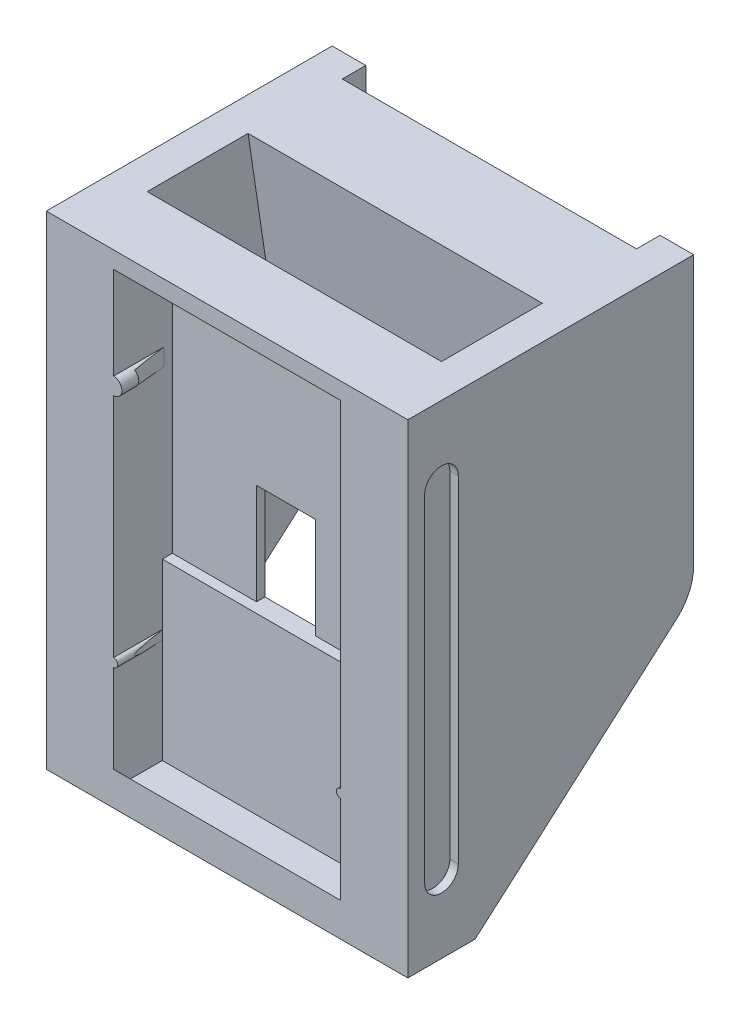
SolidWorks part; units mm, degrees
ref_plane "Front Plane" through (0, 0, 0) normal (0, 0, 1) x (1, 0, 0)
ref_plane "Top Plane" through (0, 0, 0) normal (0, 1, 0) x (1, 0, 0)
ref_plane "Right Plane" through (0, 0, 0) normal (1, 0, 0) x (0, 0, -1)
sketch "Sketch2" plane through (0, 0, 0) normal (0, 0, 1) x (1, 0, 0)
  line L1 (-6.75, -13.375) -> (6.75, -13.375) construction
  line L2 (-6.75, -13.375) -> (-6.75, 13.375)
  line L3 (-6.75, 13.375) -> (6.75, 13.375)
  line L4 (6.75, -13.375) -> (6.75, 13.375)
  line L5 (-6.75, -13.375) -> (6.75, 13.375) construction
  line L6 (-6.75, 13.375) -> (6.75, -13.375) construction
  line L13 (-1.75, 3) -> (1.75, 3)
  line L14 (-1.75, 3) -> (-1.75, -3)
  line L15 (-1.75, -3) -> (1.75, -3)
  line L16 (1.75, 3) -> (1.75, -3)
  line L17 (-1.75, 3) -> (1.75, -3) construction
  line L18 (-1.75, -3) -> (1.75, 3) construction
  line L24 (-6.75, -3) -> (6.75, -3)
  line L25 (-6.75, -3) -> (-6.75, -13.375)
  line L26 (-6.75, -13.375) -> (6.75, -13.375)
  line L27 (6.75, -3) -> (6.75, -13.375)
  point P0 (0, 0)
  point P23 (0, 0)
  dimension "D1" = 13.5
  dimension "D2" = 26.75
  dimension "D5" = 3.5
  dimension "D6" = 6
extrude "Boss-Extrude2" add sketch "Sketch2" against normal blind 0.5 contours L2 L24 L14 L13 L16 L4 L3 | L2 L26 L4 L24 L15 region at (0, -8.1875, 0) region at (0, 5.732, 0)
extrude "Boss-Extrude3" add sketch "Sketch2<5>" along normal blind 0.6 contours L2 L26 L4 L24 L15 region at (0, -8.1875, 0)
sketch "Sketch2<5>" plane through (0, 0, 0) normal (0, 0, 1) x (1, 0, 0) same geometry as "Sketch2"
sketch "Sketch4" plane through (0, 0, -0.5) normal (0, 0, -1) x (-1, 0, 0)
  line L1 (-10.75, 14.375) -> (10.75, 14.375)
  line L2 (-10.75, 14.375) -> (-10.75, -14.375)
  line L3 (-10.75, -14.375) -> (10.75, -14.375)
  line L4 (6.75, -13.375) -> (6.75, 13.375)
  line L5 (6.75, 13.375) -> (-6.75, 13.375)
  line L6 (-6.75, 13.375) -> (-6.75, -13.375)
  line L7 (-6.75, -13.375) -> (6.75, -13.375)
  line L8 (6.75, -13.375) -> (6.75, 13.375)
  line L9 (6.75, 13.375) -> (-6.75, 13.375)
  line L10 (-6.75, 13.375) -> (-6.75, -13.375)
  line L11 (-6.75, -13.375) -> (6.75, -13.375)
  line L12 (10.75, 14.375) -> (10.75, -14.375)
  line L13 (-10.75, 14.375) -> (10.75, -14.375) construction
  line L14 (-10.75, -14.375) -> (10.75, 14.375) construction
  point P2 (0, 0)
  line M13 (6.75, -13.375) -> (6.75, 13.375)
  line M14 (6.75, 13.375) -> (-6.75, 13.375)
  line M15 (-6.75, 13.375) -> (-6.75, -13.375)
  line M16 (-6.75, -13.375) -> (6.75, -13.375)
  dimension "D2" = 4
  dimension "D3" = 1
  dimension "D1" = 0
extrude "Boss-Extrude4" add sketch "Sketch4" against normal blind 3 contours L12 L1 L2 L3 M13 M16 M15 M14 region at (0, 14.016, -0.5)
sketch "Sketch5" plane through (0, 0, 2.5) normal (0, 0, 1) x (1, 0, 0)
  line L1 (-6.75, -13.375) -> (-6.75, -3) construction
  line L2 (6.75, 13.375) -> (6.75, -13.375) construction
  line L3 (-6.75, -13.375) -> (-6.75, 13.375) construction
  line L4 (-10.75, 14.375) -> (-10.75, -14.375)
  line L5 (-10.75, -14.375) -> (10.75, -14.375)
  line L6 (10.75, -14.375) -> (10.75, 14.375)
  line L7 (10.75, 14.375) -> (-10.75, 14.375)
  line L8 (-10.75, 14.375) -> (-10.75, -14.375)
  line L9 (-10.75, -14.375) -> (10.75, -14.375)
  line L10 (10.75, -14.375) -> (10.75, 14.375)
  line L11 (10.75, 14.375) -> (-10.75, 14.375)
  line L12 (-6.75, -13.375) -> (6.75, -13.375) construction
  line L13 (-6.75, 13.375) -> (6.75, 13.375) construction
  line L14 (-6.75, -7.125) -> (-6.75, -11.375)
  line L15 (-6.75, -11.375) -> (6.75, -11.375)
  line L16 (6.75, -11.375) -> (6.75, -7.125)
  line L17 (6.75, -6.625) -> (6.75, 13.375)
  line L18 (6.75, 13.375) -> (-6.75, 13.375)
  line L19 (-6.75, 13.375) -> (-6.75, 7.875)
  line L20 (-6.75, 6.875) -> (-6.75, -6.625)
  line L21 (6.75, -13.375) -> (-6.75, -13.375) construction
  arc A0 (-6.75, -7.125) -> (-6.75, -6.625) centre (-6.75, -6.875) ccw
  arc A1 (6.75, -6.625) -> (6.75, -7.125) centre (6.75, -6.875) ccw
  arc A2 (-6.75, 6.875) -> (-6.75, 7.875) centre (-6.75, 7.375) ccw
  dimension "D3" = 0.5
  dimension "D4" = 1
  dimension "D2" = 6.5
  dimension "D5" = 6
  dimension "D6" = 2
  dimension "D1" = 0
extrude "Boss-Extrude5" add sketch "Sketch5" along normal blind 1
chamfer "Chamfer1" distance 2 distance2 0.25 3 edges at (6.75, -6.875, 2.5) (-6.75, -6.875, 2.5) (-6.75, 7.375, 2.5) first distance on face at (6.75, -4.6875, 2.1) first distance on face at (-6.75, -1.6719, 2.325)
chamfer "Chamfer2" distance 2 angle 45 1 edges at (0, -11.375, 2.5)
sketch "Sketch7" plane through (10.75, 0, 0) normal (1, 0, 0) x (0, 0, -1)
  line L0 (-1.5, 10) -> (-1.5, -10) construction
  line L1 (-0.5, 10) -> (-0.5, -10)
  line L2 (-2.5, 10) -> (-2.5, -10)
  line L3 (0.5, 14.375) -> (0.5, -14.375) construction
  arc A0 (-0.5, 10) -> (-2.5, 10) centre (-1.5, 10) ccw
  arc A1 (-2.5, -10) -> (-0.5, -10) centre (-1.5, -10) ccw
  point P2 (-1.5, 0)
  point P7 (0, 0)
  dimension "D1" = 20
  dimension "D2" = 2
  dimension "D3" = 2
extrude "Cut-Extrude3" cut sketch "Sketch7" against normal blind 0.5
sketch "Sketch8" plane through (10.75, 0, 0) normal (1, 0, 0) x (0, 0, -1)
  line L3 (0.5, -14.375) -> (0.5, 14.375)
  line L4 (0.5, 14.375) -> (0.5, -14.375) construction
  line L5 (-3.5, -14.375) -> (0.5, -14.375) construction
  line L6 (0.5, -14.375) -> (12.477, -3.8815)
  line L7 (8.9174, -1.8606) -> (6.5, 14.375)
  line L8 (12.1, -1.625) -> (12.1, 14.375)
  line L9 (0.5, 14.375) -> (13.5, 14.375)
  line L10 (13.5, 14.375) -> (13.5, -1.625)
  arc A1 (8.9174, -1.8606) -> (12.1, -1.625) centre (10.5, -1.625) ccw
  arc A2 (12.477, -3.8815) -> (13.5, -1.625) centre (10.5, -1.625) ccw
  arc A3 (9.361, -4.4004) -> (12.477, -3.8815) centre (10.5, -1.625) ccw construction
  arc A4 (13.5, -1.625) -> (9.361, -4.4004) centre (10.5, -1.625) ccw construction
  arc A5 (10.5, -0.025) -> (8.9174, -1.8606) centre (10.5, -1.625) ccw construction
  arc A6 (12.1, -1.625) -> (10.5, -0.025) centre (10.5, -1.625) ccw construction
  point P7 (8.9, 14.375)
  point P15 (10.5, -1.7508)
  point P16 (0, 0)
  point P17 (9.361, -4.4004)
  point P22 (13.5, -1.625)
  point P23 (0, 0)
  point P24 (8.9, 13.269)
  point P25 (5.7955, 14.375)
  line M9 (0.5, -14.375) -> (0.5, 14.375)
  dimension "D3" = 3.2
  dimension "D1" = 6
  dimension "D2" = 10
  dimension "D4" = 16
  dimension "D5" = 6
extrude "Boss-Extrude6" add sketch "Sketch8" against normal blind 2 contours L6 A2 L8 A1 L7 M9 | L7 A1 L8 region at (10.75, 1.3011, -5.3258) region at (10.75, 6.5884, -9.8774)
mirror "Mirror1" about plane through (0, 0, 0) normal (1, 0, 0) of "Boss-Extrude6", "Cut-Extrude3"
extrude "Boss-Extrude8" add sketch "Sketch8<3>" against normal up to surface (19.5 mm away) from surface contours L7 A1 L8 region at (10.75, 6.5884, -9.8774) up to face at (-8.75, 1.7516, -8.1442) starting at face at (8.75, 1.7516, -8.1442)
sketch "Sketch8<3>" plane through (10.75, 0, 0) normal (1, 0, 0) x (0, 0, -1) same geometry as "Sketch8"
